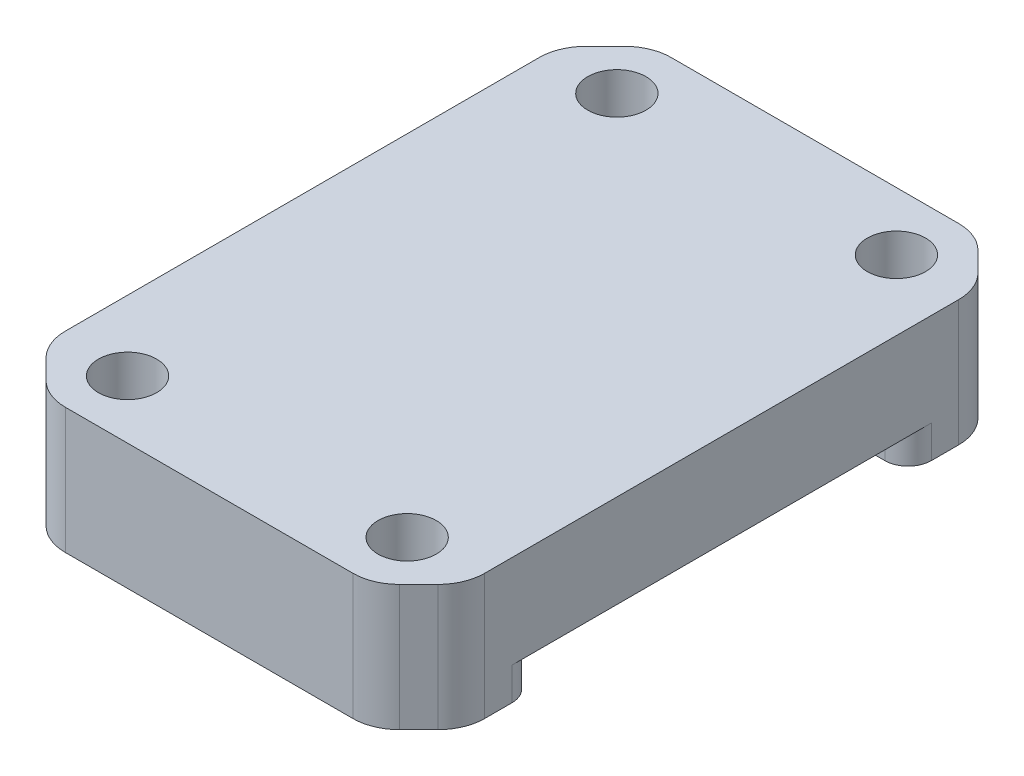
SolidWorks part; units mm, degrees
ref_plane "前视基准面" through (0, 0, 0) normal (0, 0, 1) x (1, 0, 0)
ref_plane "上视基准面" through (0, 0, 0) normal (0, 1, 0) x (1, 0, 0)
ref_plane "右视基准面" through (0, 0, 0) normal (1, 0, 0) x (0, 0, -1)
sketch "草图1" plane through (0, 0, 0) normal (0, 0, 1) x (1, 0, 0)
  line L1 (13.5, 6.4) -> (16.5, 6.4)
  line L2 (13.5, 6.4) -> (13.5, 3)
  line L3 (13.5, 3) -> (16.5, 3)
  line L4 (16.5, 6.4) -> (16.5, 3)
  line L5 (13.5, 6.4) -> (16.5, 3) construction
  line L6 (13.5, 3) -> (16.5, 6.4) construction
  line L7 (15, 4.7) -> (15, 4) construction
  line L9 (13.5, 4.4) -> (16.5, 4.4)
  line L10 (15, 4.4) -> (15, 4.53) construction
  line L11 (15.944, 4.9665) -> (16.0825, 4.6669)
  line L12 (14.056, 4.9665) -> (13.9175, 4.6669)
  arc A0 (15.944, 4.9665) -> (14.056, 4.9665) centre (15, 4.53) ccw
  arc A1 (13.5, 4.4) -> (13.9175, 4.6669) centre (13.5, 4.86) ccw
  arc A2 (16.0825, 4.6669) -> (16.5, 4.4) centre (16.5, 4.86) ccw
  point P0 (15, 4.7)
  dimension "D4" = 0.13
  dimension "D5" = 2.08
  dimension "D6" = 0.92
  dimension "D1" = 3.4
  dimension "D2" = 2
  dimension "D3" = 3
extrude "凸台-拉伸1" add sketch "草图1" along normal blind 16 contours L11 A2 L4 L1 L2 A1 L12 A0 region at (15, 5.6711, 0)
pattern_linear "阵列(线性)1" count 6 spacing 3 along (-1, 0, 0) of "凸台-拉伸1"
sketch "草图2" plane through (0, 6.4, 0) normal (0, 1, 0) x (1, 0, 0)
  line L1 (-1.5, 0) -> (16.5, 0)
  line L2 (-1.5, 0) -> (-1.5, -16)
  line L3 (-1.5, -16) -> (16.5, -16)
  line L4 (16.5, 0) -> (16.5, -16)
extrude "凸台-拉伸2" add sketch "草图2" along normal blind 2
sketch "草图3" plane through (0, 0, 16) normal (0, 0, 1) x (1, 0, 0)
  line L0 (16.5, 8.4) -> (16.5, 4.4) construction
  line L1 (-1.5, 8.4) -> (16.5, 8.4)
  line L2 (-1.5, 8.4) -> (-1.5, 3)
  line L3 (-1.5, 3) -> (16.5, 3)
  line L4 (16.5, 8.4) -> (16.5, 3)
  dimension "D1" = 5.4
extrude "凸台-拉伸3" add sketch "草图3" along normal blind 5
ref_plane "基准面1" through (0, 0, 8) normal (0, 0, -1) x (-1, 0, 0)
mirror "镜向1" about plane through (0, 0, 8) normal (0, 0, -1) of "凸台-拉伸3"
sketch "草图4" plane through (0, 8.4, 0) normal (0, 1, 0) x (1, 0, 0)
  line L0 (-1.5, -8) -> (16.5, -8) construction
  line L1 (-1.5, -21) -> (-1.5, -16) construction
  line L2 (16.5, -21) -> (-1.5, -21) construction
  line L3 (13.5, -18.5) -> (1.5, -18.5) construction
  line L4 (7.5, -18.5) -> (7.5, 2.5) construction
  line L5 (-1.5, 5) -> (-1.5, -21) construction
  line L6 (16.5, -21) -> (16.5, 5) construction
  line L7 (7.5, 5) -> (7.5, -21) construction
  line L8 (16.5, 5) -> (-1.5, 5) construction
  line L9 (16.5, -21) -> (-1.5, -21) construction
  line L10 (13.5, -18.5) -> (13.5, 2.5) construction
  line L11 (13.5, 2.5) -> (1.5, 2.5) construction
  line L12 (1.5, -18.5) -> (1.5, 2.5) construction
  line L13 (13.5, -18.5) -> (1.5, 2.5) construction
  line L14 (13.5, 2.5) -> (1.5, -18.5) construction
  circle A0 centre (1.5, 2.5) radius 1.25
  circle A1 centre (7.5, 2.5) radius 1.25 construction
  circle A2 centre (1.5, -18.5) radius 1.25
  circle A3 centre (7.5, -18.5) radius 1.25 construction
  circle A4 centre (13.5, 2.5) radius 1.25
  circle A5 centre (13.5, -18.5) radius 1.25
  point P0 (7.5, -8)
  point P16 (7.5, -8)
  point P20 (7.5, -8)
  dimension "D3" = 2.5
  dimension "D2" = 2.5
  dimension "D1" = 3
extrude "切除-拉伸1" cut sketch "草图4" against normal blind 10
chamfer "倒角1" distance 2 angle 45 4 edges at (16.5, 5.7, -5) (-1.5, 5.7, -5) (-1.5, 5.7, 21) (16.5, 5.7, 21)
fillet "圆角1" radius 2 8 edges at (16.5, 5.7, -3) (14.5, 5.7, -5) (-1.5, 5.7, -3) (0.5, 5.7, -5) (16.5, 5.7, 19) (14.5, 5.7, 21) (-1.5, 5.7, 19) (0.5, 5.7, 21)
fillet "圆角2" radius 1 4 edges at (-1.5, 3.7, 0) (16.5, 3.7, 0) (16.5, 3.7, 16) (-1.5, 3.7, 16)
